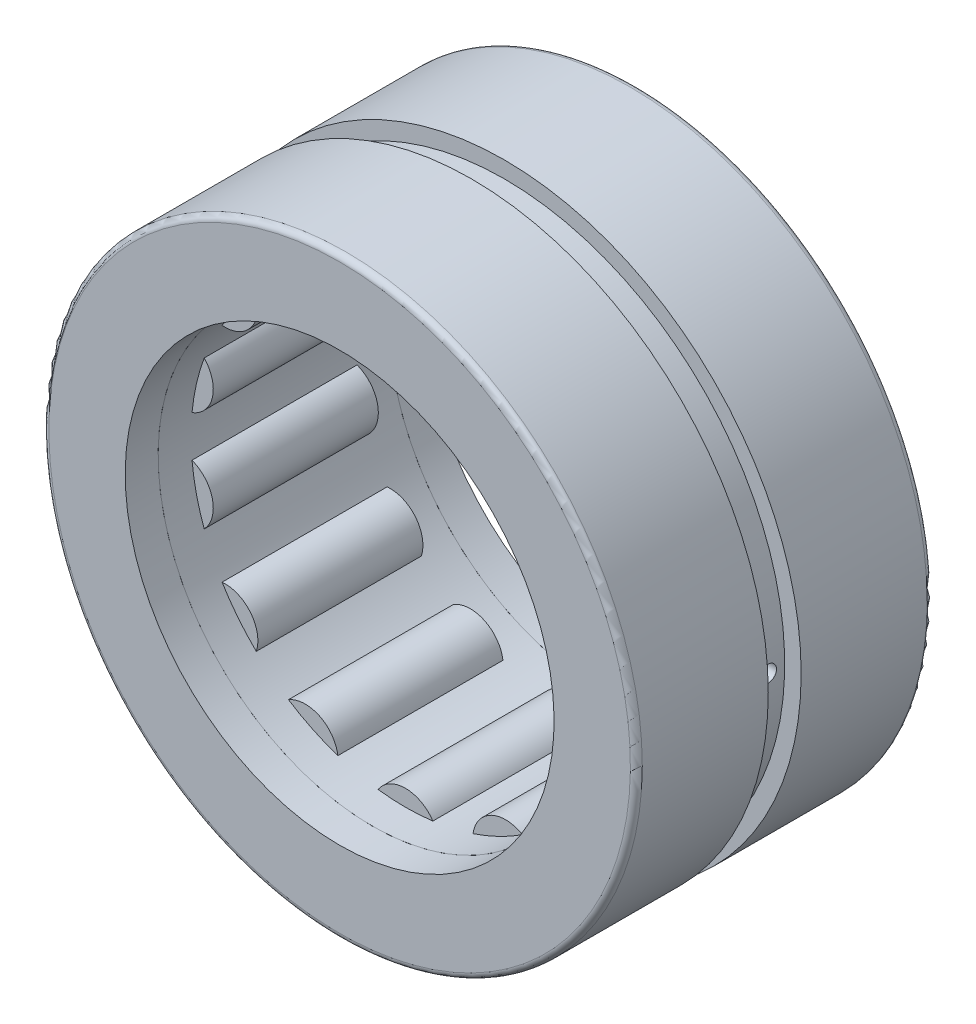
SolidWorks part; units mm, degrees
ref_plane "Front Plane" through (0, 0, 0) normal (0, 0, 1) x (1, 0, 0)
ref_plane "Top Plane" through (0, 0, 0) normal (0, 1, 0) x (1, 0, 0)
ref_plane "Right Plane" through (0, 0, 0) normal (1, 0, 0) x (0, 0, -1)
sketch "Sketch1" plane through (0, 0, 0) normal (1, 0, 0) x (0, 0, -1)
  line L0 (-9.525, 0) -> (9.525, 0) construction
  line L1 (0, 0) -> (0, 19.05) construction
  line L2 (-9.525, 0) -> (-9.525, 19.05) construction
  line L3 (-9.525, 19.05) -> (9.525, 19.05)
  line L4 (9.525, 19.05) -> (9.525, 0) construction
  line L5 (9.525, 0) -> (7.4121, 0) construction
  line L6 (7.4121, 0) -> (7.4121, 16.9371) construction
  line L7 (7.4121, 16.9371) -> (-7.4121, 16.9371)
  line L8 (-7.4121, 16.9371) -> (-7.4121, 0) construction
  line L9 (-7.4121, 0) -> (-9.525, 0) construction
  line L10 (-9.525, 19.05) -> (-9.525, 13.7679)
  line L11 (-9.525, 13.7679) -> (-7.4121, 13.7679)
  line L12 (-7.4121, 13.7679) -> (-7.4121, 16.9371)
  line L13 (7.4121, 19.05) -> (7.4121, 16.9371) construction
  line L14 (7.4121, 16.9371) -> (7.4121, 13.7679)
  line L15 (7.4121, 13.7679) -> (9.525, 13.7679)
  line L16 (9.525, 13.7679) -> (9.525, 19.05)
  line L17 (7.4121, 16.9371) -> (7.4121, 14.8243) construction
  line L18 (7.4121, 14.8243) -> (7.4121, 12.7114) construction
  line L19 (7.4121, -16.9371) -> (7.4121, -14.8243) construction
  line L20 (7.4121, -19.05) -> (7.4121, -16.9371) construction
  line L21 (9.525, -13.7679) -> (9.525, -19.05) construction
  line L22 (7.4121, -13.7679) -> (9.525, -13.7679) construction
  line L23 (7.4121, -16.9371) -> (7.4121, -13.7679) construction
  line L24 (-7.4121, -13.7679) -> (-7.4121, -16.9371) construction
  line L25 (-9.525, -13.7679) -> (-7.4121, -13.7679) construction
  line L26 (-9.525, -19.05) -> (-9.525, -13.7679) construction
  line L27 (7.4121, -16.9371) -> (-7.4121, -16.9371) construction
  line L28 (-9.525, -19.05) -> (9.525, -19.05) construction
  point P5 (0, 12.7114)
  dimension "Width" = 19.05
  dimension "OD" = 38.1
  dimension "Shaft Dia" = 25.4229
revolve "Revolve1" add sketch "Sketch1" angle 360 about L0
sketch "Sketch2" plane through (0, 0, 0) normal (1, 0, 0) x (0, 0, -1)
  line L0 (7.4121, 16.9371) -> (-7.4121, 16.9371) construction
  line L1 (-5.2993, 14.8243) -> (5.2993, 14.8243) construction
  line L2 (-5.2993, 14.8243) -> (-5.2993, 16.9371) construction
  line L3 (-5.2993, 16.9371) -> (5.2993, 16.9371)
  line L4 (5.2993, 14.8243) -> (5.2993, 16.9371) construction
  line L5 (7.4121, 13.7679) -> (9.525, 13.7679) construction
  line L6 (-7.4121, 14.8243) -> (-5.2993, 14.8243) construction
  line L7 (5.2993, 14.8243) -> (7.4121, 14.8243) construction
  line L8 (-9.525, 13.7679) -> (-7.4121, 13.7679) construction
  line L9 (-5.2993, 15.3525) -> (-5.2993, 14.2961) construction
  line L10 (-7.4121, 14.8243) -> (-7.4121, 13.7679) construction
  line L11 (-5.2993, 16.9371) -> (-5.2993, 15.3525)
  line L12 (5.2993, 16.9371) -> (5.2993, 15.3525)
  line L13 (5.2993, 15.3525) -> (-5.2993, 15.3525)
  line L14 (0, 16.9371) -> (0, 12.7114) construction
  line L15 (-7.4121, 13.7679) -> (-7.4121, 16.9371) construction
  line L16 (-5.2993, 14.2961) -> (-7.4121, 14.2961) construction
  line L17 (0, 0) -> (9.525, 0) construction
  line L18 (9.525, -19.05) -> (9.525, 19.05) construction
  line L19 (-5.2993, -14.2961) -> (-7.4121, -14.2961) construction
  line L20 (0, -16.9371) -> (0, -12.7114) construction
  line L21 (-7.4121, -14.8243) -> (-7.4121, -13.7679) construction
  line L22 (-5.2993, -15.3525) -> (-5.2993, -14.2961) construction
  line L23 (5.2993, -14.8243) -> (7.4121, -14.8243) construction
  line L24 (-7.4121, -14.8243) -> (-5.2993, -14.8243) construction
  line L25 (5.2993, -14.8243) -> (5.2993, -16.9371) construction
  line L26 (-5.2993, -14.8243) -> (-5.2993, -16.9371) construction
  line L27 (-5.2993, -14.8243) -> (5.2993, -14.8243) construction
  line L28 (5.2993, -15.3525) -> (-5.2993, -15.3525) construction
  line L29 (5.2993, -16.9371) -> (5.2993, -15.3525) construction
  line L30 (-5.2993, -16.9371) -> (-5.2993, -15.3525) construction
  line L31 (-5.2993, -16.9371) -> (5.2993, -16.9371) construction
  line L32 (-7.4121, 16.9371) -> (-7.4121, 0) construction
  point P16 (0, 14.8243)
revolve "Revolve2" add sketch "Sketch2" angle 360 about L1
sketch "Sketch3" plane through (0, 0, 0) normal (1, 0, 0) x (0, 0, -1)
  line L0 (7.4121, 16.9371) -> (7.4121, 13.7679) construction
  line L1 (-7.4121, 14.8243) -> (7.4121, 14.8243)
  line L2 (-7.4121, 14.8243) -> (-7.4121, 15.3525)
  line L3 (-7.4121, 15.3525) -> (7.4121, 15.3525)
  line L4 (7.4121, 14.8243) -> (7.4121, 15.3525)
  line L5 (0, 0) -> (9.525, 0) construction
  line L6 (9.525, -19.05) -> (9.525, 19.05) construction
  line L7 (7.4121, -14.8243) -> (7.4121, -15.3525) construction
  line L8 (-7.4121, -15.3525) -> (7.4121, -15.3525) construction
  line L9 (-7.4121, -14.8243) -> (-7.4121, -15.3525) construction
  line L10 (-7.4121, -14.8243) -> (7.4121, -14.8243) construction
revolve "Revolve3" add sketch "Sketch3" angle 360 about L1
ref_axis "Axis1" through (0, 0, -9.525) along (0, 0, 1)
pattern_circular "CirPattern1" count 14 every 25.714 about axis through (0, 0, -9.525) along (0, 0, 1) of bodies 167 166
fillet "Fillet1" radius 0.381 2 edges at (0, -19.05, -9.525) (0, -19.05, 9.525)
sketch "Sketch4" plane through (0, 0, 0) normal (1, 0, 0) x (0, 0, -1)
  line L0 (-1.0564, 19.05) -> (0, 17.9936)
  line L1 (-9.525, 19.05) -> (9.525, 19.05) construction
  line L2 (0, 0) -> (0, 19.05) construction
  line L3 (0, 17.9936) -> (1.0564, 19.05)
  line L4 (1.0564, 19.05) -> (-1.0564, 19.05)
  line L5 (0, 19.05) -> (0, 16.9371) construction
revolve "Cut-Revolve1" cut sketch "Sketch4" angle 360 about L0
sketch "Sketch5" plane through (0, 0, 7.4121) normal (0, 0, -1) x (-1, 0, 0)
  circle A0 centre (0, 0) radius 13.7679 construction
  circle A1 centre (0, 0) radius 16.9371
  circle A2 centre (0, 0) radius 16.9371 construction
  circle A3 centre (0, 0) radius 13.7679
  circle A4 centre (0, 0) radius 17.1911
  dimension "D1" = 0
  dimension "D2" = 0.254
extrude "Boss-Extrude1" add sketch "Sketch5" along normal up to surface (14.8243 mm away) separate body up to face at (0, -13.7679, -7.4121)
revolve "Cut-Revolve3" cut sketch "Sketch2<3>" angle 360 about L1
sketch "Sketch2<3>" plane through (0, 0, 0) normal (1, 0, 0) x (0, 0, -1) same geometry as "Sketch2"
pattern_circular "CirPattern2" count 14 over 360 about axis through (0, 0, -56.036) along (0, 0, 1) of "Cut-Revolve3"
sketch "Sketch6" plane through (0, 0, 0) normal (1, 0, 0) x (0, 0, -1)
  line L0 (-1.0564, 19.05) -> (1.0564, 19.05)
  line L1 (1.0564, 19.05) -> (1.0564, 17.9936)
  line L2 (1.0564, 19.05) -> (1.0564, -19.05) construction
  line L3 (1.0564, 17.9936) -> (-1.0564, 17.9936)
  line L4 (-1.0564, 19.05) -> (-1.0564, -19.05) construction
  line L5 (-1.0564, 17.9936) -> (-1.0564, 19.05)
  dimension "D1" = 2.1129
revolve "Cut-Revolve4" cut sketch "Sketch6" angle 360 about axis through (0, 0, 9.525) along (0, 0, 1)
sketch "Sketch7" plane through (0, 0, 0) normal (1, 0, 0) x (0, 0, -1)
  line L0 (-9.525, 0) -> (9.525, 0) construction
  circle A0 centre (0, 0) radius 0.5282
  dimension "D1" = 1.0564
extrude "Cut-Extrude1" cut sketch "Sketch7" along normal through all
equation "\"Angle@CirPattern1\" = 360/\"Rollers@CirPattern1\""
equation "\"Rollers@CirPattern1\" = \"OD@Sketch1\"*9"
equation "\"D1@Fillet1\" = \"OD@Sketch1\"*.01"
equation "\"D1@CirPattern2\"= \"Rollers@CirPattern1\""
equation "\"D1@Sketch7\"= \"D1@Sketch6\" * .5"
